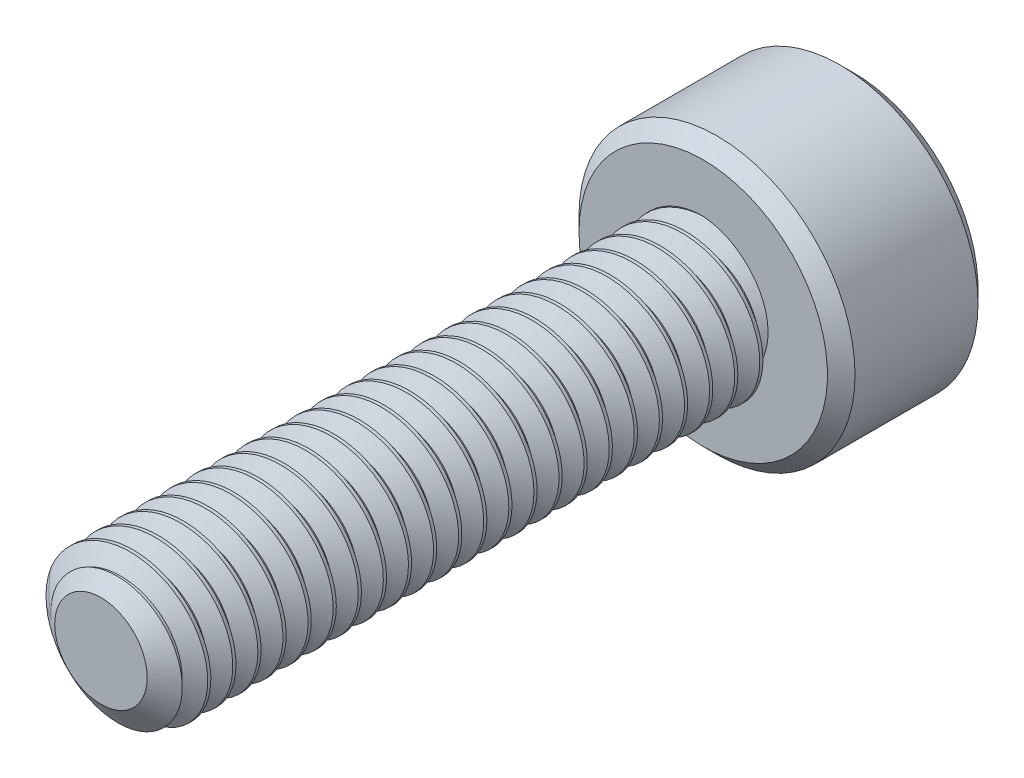
SolidWorks part; units mm, degrees
other "DetailItem1"
material "M3-12"
ref_plane "Front Plane" through (0, 0, 0) normal (0, 0, 1) x (1, 0, 0)
ref_plane "Top Plane" through (0, 0, 0) normal (0, 1, 0) x (1, 0, 0)
ref_plane "Right Plane" through (0, 0, 0) normal (1, 0, 0) x (0, 0, -1)
sketch "Sketch1" plane through (0, 0, 0) normal (0, 0, 1) x (1, 0, 0)
  circle A0 centre (0, 0) radius 1.5
  dimension "OD" = 3
extrude "Extrude1" add sketch "Sketch1" against normal blind 12
sketch "Sketch2" plane through (0, 0, 0) normal (0, 0, 1) x (1, 0, 0)
  circle A0 centre (0, 0) radius 1.5 construction
  circle A1 centre (0, 0) radius 1.5
curve "Helix/Spiral1" pitch 0.5 height 12.5 radius 1.5 centre (0, 0, 0) axis (0, 0, -1) start towards (0, 1, 0) parameters "pitch"=0.5
sketch "Sketch3" plane through (0, 0, 0) normal (1, 0, 0) x (0, 0, -1)
  line L0 (-0.4375, 1.5) -> (-0.25, 1.1752)
  line L1 (-0.25, 1.1752) -> (-0.1875, 1.1752)
  line L2 (-0.1875, 1.1752) -> (0, 1.5)
  line L3 (-0.4375, 1.5) -> (0, 1.5)
  line L4 (-0.2188, 1.5) -> (-0.2188, 1.1752) construction
  line L5 (-0.3438, 1.3376) -> (-0.0938, 1.3376) construction
  line L6 (0, 1.5) -> (0, -1.5) construction
  dimension "D1" = 0.0625
  dimension "D2" = 0.25
  dimension "D3" = 60
sweep "Cut-Sweep1" cut profiles "Sketch3" path "Helix/Spiral1" align with end faces yes
sketch "Sketch4" plane through (0, 0, 0) normal (1, 0, 0) x (0, 0, -1)
  line L0 (0.4053, 1.5) -> (0, 0.9212)
  line L1 (0, 0.9212) -> (0, 1.5)
  line L2 (0.4053, 1.5) -> (0, 1.5)
  line L3 (-0.4375, 1.5) -> (0, 1.5) construction
  line L4 (0, 0) -> (7.0209, 0) construction
  dimension "D1" = 55
  dimension "D2" = 0.254
revolve "Cut-Revolve1" cut sketch "Sketch4" angle 360 about L4
sketch "Sketch6" plane through (0, 0, -12) normal (0, 0, -1) x (-1, 0, 0)
  circle A0 centre (0, 0) radius 2.75
  dimension "head dia" = 5.5
extrude "Extrude2" add sketch "Sketch6" along normal blind 3
sketch "Sketch7" plane through (0, 0, -15) normal (0, 0, -1) x (-1, 0, 0)
  line L1 (0, 1.4434) -> (-1.25, 0.7217)
  line L2 (-1.25, 0.7217) -> (-1.25, -0.7217)
  line L3 (-1.25, -0.7217) -> (0, -1.4434)
  line L4 (0, -1.4434) -> (1.25, -0.7217)
  line L5 (1.25, -0.7217) -> (1.25, 0.7217)
  line L6 (1.25, 0.7217) -> (0, 1.4434)
  circle A0 centre (0, 0) radius 1.25 construction
  dimension "hex dia" = 2.5
extrude "Cut-Extrude1" cut sketch "Sketch7" against normal blind 1.875
sketch "Sketch8" plane through (0, 0, -15) normal (0, 0, -1) x (-1, 0, 0)
  circle A0 centre (0, 0) radius 1.4434
extrude "Cut-Extrude2" cut sketch "Sketch8" against normal through all draft 45
chamfer "Chamfer1" distance 0.275 angle 45 2 edges at (-2.75, 0, -15) (-2.75, 0, -12)
sketch "Sketch10" plane through (0, 0, -12) normal (0, 0, 1) x (1, 0, 0)
  circle A1 centre (0, 0) radius 1.5
  circle A2 centre (0, 0) radius 1.5
  dimension "D1" = 0
ref_plane "Plane1" through (0, 0, -22) normal (0, 0, 1) x (1, 0, 0)
extrude "partial thread" [suppressed] add sketch "Sketch10" along normal up to surface (58 mm away) separate body up to plane "Plane1"
chamfer "Chamfer2" [suppressed] distance 0.06 angle 45
combine bodies "Combine1" [suppressed] operation type add bodies to combine 107 108
sketch "Sketch9" plane through (0, 0, 0) normal (1, 0, 0) x (0, 0, -1)
  line L0 (0, 1.5) -> (0, -1.5) construction
  line L1 (1.25, 1.5) -> (1.25, -1.5) construction
  dimension "D1" = 1.25
equation "\"D3@Helix/Spiral1\" = \"screw length@Extrude1\"+\"pitch@Helix/Spiral1\""
equation "\"D1@Sketch3\" = \"pitch@Helix/Spiral1\"*.125"
equation "\"D2@Sketch3\" = \"pitch@Helix/Spiral1\"*.5"
equation "\"D1@Cut-Extrude1\" = \"hex dia@Sketch7\"*.75"
equation "\"D1@Chamfer1\" = \"head dia@Sketch6\"*.05"
equation "\"D1@Sketch9\" = \"pitch@Helix/Spiral1\"*2.5"
equation "\"D1@Chamfer2\"=\"OD@Sketch1\"*.02"
